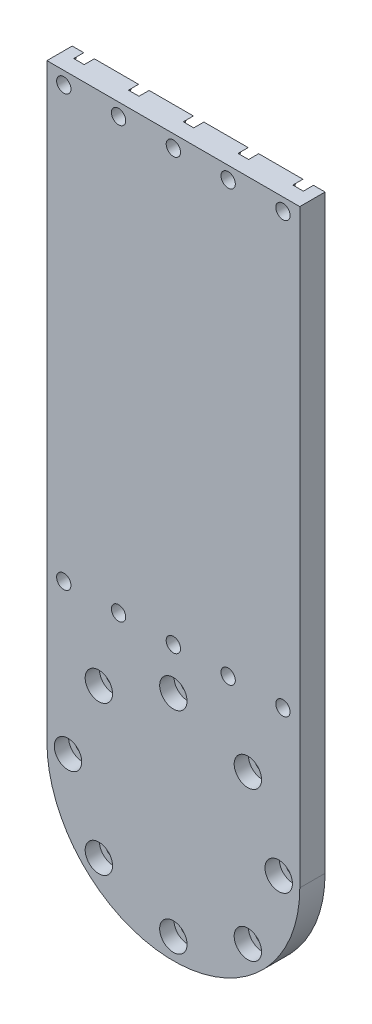
SolidWorks part; units mm, degrees
material "6061-T6 (SS)"
ref_plane "Front Plane" through (0, 0, 0) normal (0, 0, 1) x (1, 0, 0)
ref_plane "Top Plane" through (0, 0, 0) normal (0, 1, 0) x (1, 0, 0)
ref_plane "Right Plane" through (0, 0, 0) normal (1, 0, 0) x (0, 0, -1)
sketch "Sketch1" plane through (0, 0, 0) normal (0, 0, 1) x (1, 0, 0)
  line L0 (-30, 0) -> (-30, 140)
  line L1 (-30, 140) -> (30, 140)
  line L2 (30, 140) -> (30, 0)
  arc A0 (-30, 0) -> (30, 0) centre (0, 0) ccw
  dimension "D1" = 60
  dimension "D2" = 140
extrude "Boss-Extrude1" add sketch "Sketch1" along normal blind 6
sketch "Sketch2" plane through (0, 0, 6) normal (0, 0, 1) x (1, 0, 0)
  circle A0 centre (0, 0) radius 25
  point P6 (0, 25)
  point P12 (17.6777, 17.6777)
  point P13 (25, 0)
  point P14 (17.6777, -17.6777)
  point P15 (0, -25)
  point P16 (-17.6777, -17.6777)
  point P17 (-25, 0)
  point P18 (-17.6777, 17.6777)
  dimension "D1" = 50
  dimension "D2" = 8
hole_wizard "CBORE for M3 Hex Socket Head Cap Screw1" positions "Sketch2" profile "Sketch3" counterbore size "M3" standard "DIN" end condition through all
sketch "Sketch3" plane through (-17.6777, 17.6777, 6) normal (1, 0, 0) x (0, -1, 0)
  line L0 (0, 0) -> (0, 6)
  line L1 (0, 6) -> (1.7, 6)
  line L3 (1.7, 6) -> (1.7, 3.4)
  line L4 (1.7, 3.4) -> (3.25, 3.4)
  line L5 (3.25, 3.4) -> (3.25, 0)
  line L7 (3.25, 0) -> (0, 0)
  line L11 (0, -6.35) -> (0, 107.95) construction
  dimension "Thru Hole Dia." = 3.4
  dimension "Thru Hole Depth" = 6
  dimension "C'Bore Dia." = 6.5
  dimension "C'Bore Depth" = 3.4
sketch "Sketch4" plane through (0, 0, 0) normal (0, 0, -1) x (-1, 0, 0)
  line L0 (-30, 35) -> (30, 35) construction
  line L1 (30, 140) -> (30, 0) construction
  line L2 (-30, 0) -> (-30, 140) construction
  line L3 (-30, 140) -> (30, 140) construction
  line L4 (0, 140) -> (0, 137) construction
  point P7 (0, 35)
  point P23 (13, 35)
  point P24 (26, 35)
  point P25 (0, 35)
  point P26 (13, 35)
  point P27 (-13, 35)
  point P28 (0, 35)
  point P29 (-13, 35)
  point P30 (-26, 35)
  point P46 (0, 137)
  point P59 (13, 137)
  point P60 (26, 137)
  point P61 (0, 137)
  point P62 (13, 137)
  point P63 (-13, 137)
  point P64 (0, 137)
  point P65 (-13, 137)
  point P66 (-26, 137)
  point P71 (0, 0)
  dimension "D1" = 35
  dimension "D5" = 3
  dimension "D4" = 3
  dimension "D3" = 3
  dimension "D2" = 3
hole_wizard "CBORE for M3 Hex Socket Thin Head Cap Screw1" positions "Sketch4" profile "Sketch6" counterbore size "M3" standard "DIN"
sketch "Sketch6" plane through (26, 137, 0) normal (1, 0, 0) x (0, 1, 0)
  line L0 (0, 0) -> (0, 11.0215)
  line L1 (0, 11.0215) -> (1.7, 10)
  line L2 (1.7, 10) -> (1.7, 2.4)
  line L3 (1.7, 2.4) -> (3.25, 2.4)
  line L4 (3.25, 2.4) -> (3.25, 0)
  line L5 (3.25, 0) -> (0, 0)
  line L10 (0, 11.0215) -> (-1.7, 10) construction
  line L11 (0, -6.35) -> (0, 107.95) construction
  dimension "Hole Dia." = 3.4
  dimension "Hole Depth" = 10
  dimension "C'Bore Dia." = 6.5
  dimension "C'Bore Depth" = 2.4
  dimension "Drill Angle" = 118
